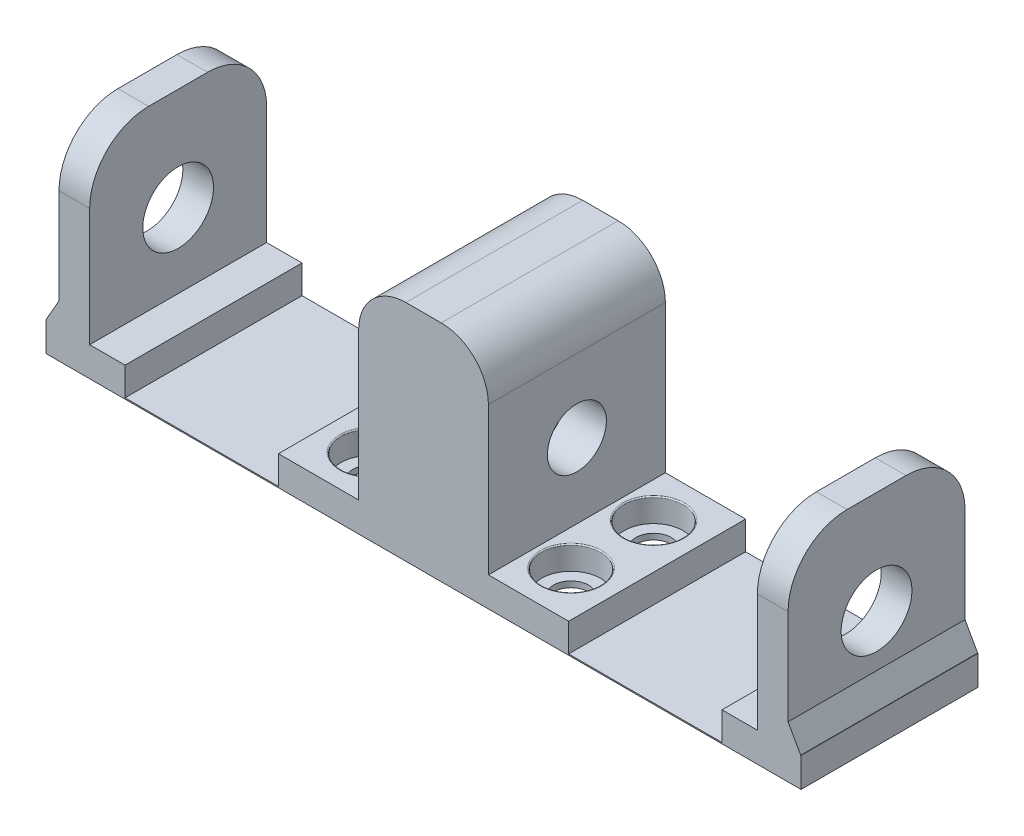
SolidWorks part; units mm, degrees
ref_plane "Alzado" through (0, 0, 0) normal (0, 0, 1) x (1, 0, 0)
ref_plane "Planta" through (0, 0, 0) normal (0, 1, 0) x (1, 0, 0)
ref_plane "Vista lateral" through (0, 0, 0) normal (1, 0, 0) x (0, 0, -1)
sketch "Croquis1" plane through (0, 0, 0) normal (0, 0, 1) x (1, 0, 0)
  line L0 (0, 9.5) -> (0, -9.5) construction
  line L1 (-1.5, 9.5) -> (1.5, 9.5)
  line L2 (-5.5, 5.5) -> (-5.5, -7)
  line L3 (-5.5, -9.5) -> (5.5, -9.5)
  line L4 (5.5, 5.5) -> (5.5, -7)
  line L5 (-5.5, 9.5) -> (5.5, -9.5) construction
  line L6 (-5.5, -9.5) -> (5.5, 9.5) construction
  line L7 (-5.5, -9.5) -> (-11.5, -9.5)
  line L9 (-5.5, -7) -> (-11.5, -7)
  line L10 (-11.5, -9.5) -> (-11.5, -7)
  line L11 (5.5, -7) -> (11.5, -7)
  line L12 (11.5, -9.5) -> (11.5, -7)
  line L13 (5.5, -9.5) -> (11.5, -9.5)
  arc A0 (5.5, 5.5) -> (1.5, 9.5) centre (1.5, 5.5) ccw
  arc A1 (-5.5, 5.5) -> (-1.5, 9.5) centre (-1.5, 5.5) cw
  point P0 (0, 0)
  dimension "D1" = 4
  dimension "D2" = 6
  dimension "D3" = 2.5
  dimension "D4" = 11
  dimension "D5" = 15
extrude "Saliente-Extruir1" add sketch "Croquis1" against normal blind 15
sketch "Croquis2" plane through (5.5, 0, 0) normal (1, 0, 0) x (0, 0, -1)
  line L0 (7.5, 9.5) -> (7.5, -7) construction
  line L1 (15, 9.5) -> (0, 9.5) construction
  line L2 (15, -7) -> (0, -7) construction
  line L3 (15, -9.5) -> (0, -9.5) construction
  circle A0 centre (7.5, -0.68) radius 2.5
  dimension "D2" = 5
  dimension "D1" = 8.82
extrude "Cortar-Extruir1" cut sketch "Croquis2" against normal blind 3.5
sketch "Croquis3" plane through (-5.5, 0, 0) normal (-1, 0, 0) x (0, 0, 1)
  line L0 (-7.5, 9.5) -> (-7.5, -7) construction
  line L1 (-15, 9.5) -> (0, 9.5) construction
  line L2 (-15, -7) -> (0, -7) construction
  line L3 (-15, -9.5) -> (0, -9.5) construction
  circle A0 centre (-7.5, -0.68) radius 2.5
  dimension "D2" = 5
  dimension "D1" = 8.82
extrude "Cortar-Extruir2" cut sketch "Croquis3" against normal blind 3.5
sketch "Croquis4" plane through (0, -7, 0) normal (0, 1, 0) x (1, 0, 0)
  line L0 (0, 15) -> (0, 0) construction
  line L1 (1.5, 15) -> (-1.5, 15) construction
  line L2 (-8.5, 15) -> (-8.5, 0) construction
  line L3 (-5.5, 15) -> (-11.5, 15) construction
  line L4 (-5.5, 0) -> (-11.5, 0) construction
  circle A0 centre (-8.5, 11) radius 2.5
  circle A1 centre (-8.5, 4) radius 2.5
  circle A2 centre (8.5, 4) radius 2.5
  circle A3 centre (8.5, 11) radius 2.5
  dimension "D1" = 5
  dimension "D2" = 4
  dimension "D3" = 4
extrude "Cortar-Extruir3" cut sketch "Croquis4" against normal blind 2
fillet "Redondeo1" radius 0.1 4 edges at (11, -7, -4) (11, -7, -11) (-11, -7, -4) (-11, -7, -11)
sketch "Croquis5" plane through (0, -7, 0) normal (0, 1, 0) x (1, 0, 0)
  line L0 (-8.5, 15) -> (-8.5, 0) construction
  line L1 (-5.5, 15) -> (-11.5, 15) construction
  line L2 (-5.5, 0) -> (-11.5, 0) construction
  line L3 (0, 15) -> (0, 0) construction
  line L4 (1.5, 15) -> (-1.5, 15) construction
  line L5 (1.5, 0) -> (-1.5, 0) construction
  circle A0 centre (-8.5, 11) radius 1.5
  circle A1 centre (-8.5, 4) radius 1.5
  circle A2 centre (-8.5, 11) radius 2.6 construction
  circle A3 centre (8.5, 4) radius 1.5
  circle A4 centre (8.5, 11) radius 1.5
  dimension "D1" = 3
extrude "Cortar-Extruir4" cut sketch "Croquis5" against normal through all
sketch "Croquis6" plane through (-11.5, 0, 0) normal (-1, 0, 0) x (0, 0, 1)
  line L1 (-15, -7) -> (0, -7)
  line L2 (-15, -7) -> (-15, -9.5)
  line L3 (-15, -9.5) -> (0, -9.5)
  line L4 (0, -7) -> (0, -9.5)
extrude "Saliente-Extruir2" add sketch "Croquis6" along normal blind 20.5
sketch "Croquis7" plane through (11.5, 0, 0) normal (1, 0, 0) x (0, 0, -1)
  line L1 (0, -7) -> (15, -7)
  line L2 (0, -7) -> (0, -9.5)
  line L3 (0, -9.5) -> (15, -9.5)
  line L4 (15, -7) -> (15, -9.5)
extrude "Saliente-Extruir3" add sketch "Croquis7" along normal blind 20.5
sketch "Croquis8" plane through (0, -7, 0) normal (0, 1, 0) x (1, 0, 0)
  line L0 (-5.5, 15) -> (-32, 15) construction
  line L1 (-30.9, 15) -> (-28.3, 15)
  line L2 (-30.9, 15) -> (-30.9, 0)
  line L3 (-30.9, 0) -> (-28.3, 0)
  line L4 (-28.3, 15) -> (-28.3, 0)
  line L5 (-5.5, 0) -> (-32, 0) construction
  line L6 (0, 15) -> (0, 0) construction
  line L7 (1.5, 15) -> (-1.5, 15) construction
  line L8 (30.9, 0) -> (28.3, 0)
  line L9 (28.3, 15) -> (28.3, 0)
  line L10 (30.9, 15) -> (28.3, 15)
  line L11 (30.9, 15) -> (30.9, 0)
  line L12 (-32, 0) -> (-32, 15) construction
  dimension "D1" = 2.6
  dimension "D2" = 1.1
extrude "Saliente-Extruir4" add sketch "Croquis8" along normal blind 15
fillet "Redondeo4" radius 5 2 edges at (-29.6, 8, -15) (-29.6, 8, 0)
fillet "Redondeo5" radius 5 2 edges at (29.6, 8, -15) (29.6, 8, 0)
ref_plane "Plano12" through (0, 0, -7.5) normal (0, 0, 1) x (1, 0, 0)
sketch "Croquis17" plane through (0, 0, -7.5) normal (0, 0, 1) x (1, 0, 0)
  line L0 (30.9, -5.0818) -> (31.9724, -7)
  line L1 (30.9, 3) -> (30.9, -7) construction
  line L3 (32, -7) -> (30.9, -7) construction
rib "Nervio1" sketch "Croquis17" sketch "Croquis17" thickness 15 extrusion direction parallel to sketch draft on no parameters "D1"=15
sketch "Croquis22" plane through (0, 0, -7.5) normal (0, 0, 1) x (1, 0, 0)
  line L0 (-31.9933, -7) -> (-30.9, -5.0818)
  line L1 (-30.9, -7) -> (-32, -7) construction
  line L2 (-30.9, 8) -> (-30.9, 3) construction
  line L4 (-30.9, 3) -> (-30.9, -7) construction
rib "Nervio2" sketch "Croquis22" sketch "Croquis22" thickness 15 extrusion direction parallel to sketch draft on no parameters "D1"=15
sketch "Croquis23" plane through (30.9, 0, 0) normal (1, 0, 0) x (0, 0, -1)
  line L0 (7.5, 8) -> (7.5, -5.0818) construction
  line L1 (5, 8) -> (10, 8) construction
  line L2 (0, -5.0818) -> (15, -5.0818) construction
  line L3 (0, -9.5) -> (15, -9.5) construction
  circle A0 centre (7.5, -0.68) radius 3
  dimension "D1" = 6
  dimension "D2" = 8.82
extrude "Cortar-Extruir5" cut sketch "Croquis23" against normal blind 7
sketch "Croquis24" plane through (-30.9, 0, 0) normal (-1, 0, 0) x (0, 0, 1)
  line L0 (-7.5, 8) -> (-7.5, -5.0818) construction
  line L1 (-10, 8) -> (-5, 8) construction
  line L2 (-15, -5.0818) -> (0, -5.0818) construction
  line L3 (-15, -9.5) -> (0, -9.5) construction
  circle A0 centre (-7.5, -0.68) radius 3
  dimension "D1" = 6
  dimension "D2" = 8.82
extrude "Cortar-Extruir6" cut sketch "Croquis24" against normal blind 7
sketch "Croquis34" plane through (0, 0, 0) normal (0, 0, 1) x (1, 0, 0)
  line L0 (-28.3, -7) -> (-25.3, -7)
  line L1 (-5.5, -7) -> (-28.3, -7) construction
  line L2 (-25.3, -7) -> (-25.3, -9.4)
  line L3 (-25.3, -9.4) -> (-12.3, -9.4)
  line L4 (-12.3, -9.4) -> (-12.3, -7)
  line L5 (-25.3, -7) -> (-12.3, -7)
  line L6 (0, -9.5) -> (0, 0) construction
  line L7 (-32, -9.5) -> (32, -9.5) construction
  line L8 (25.3, -7) -> (25.3, -9.4)
  line L9 (25.3, -9.4) -> (12.3, -9.4)
  line L10 (12.3, -9.4) -> (12.3, -7)
  line L11 (25.3, -7) -> (12.3, -7)
  line M23 (-5.5, -7) -> (-28.3, -7)
  dimension "D1" = 13
  dimension "D2" = 3
  dimension "D3" = 2.4
extrude "Cortar-Extruir7" cut sketch "Croquis34" against normal through all contours L3 L4 L2 M23 | L11 L10 L9 L8 region at (-18.8, -8.2, 0)
sketch "Croquis35" plane through (0, -9.5, 0) normal (0, -1, 0) x (1, 0, 0)
  line L0 (-30, 0) -> (-30, -15) construction
  line L1 (-32, 0) -> (32, 0) construction
  line L2 (-32, -15) -> (32, -15) construction
  line L3 (-32, -15) -> (-32, 0) construction
  line L4 (0, 0) -> (0, -15) construction
  circle A0 centre (-30, -4) radius 1.5
  circle A1 centre (-30, -11) radius 1.5
  circle A2 centre (30, -11) radius 1.5
  circle A3 centre (30, -4) radius 1.5
  dimension "D2" = 3
  dimension "D3" = 4
  dimension "D1" = 2
  dimension "D4" = 4
extrude "Cortar-Extruir8" cut sketch "Croquis35" against normal blind 2.2
